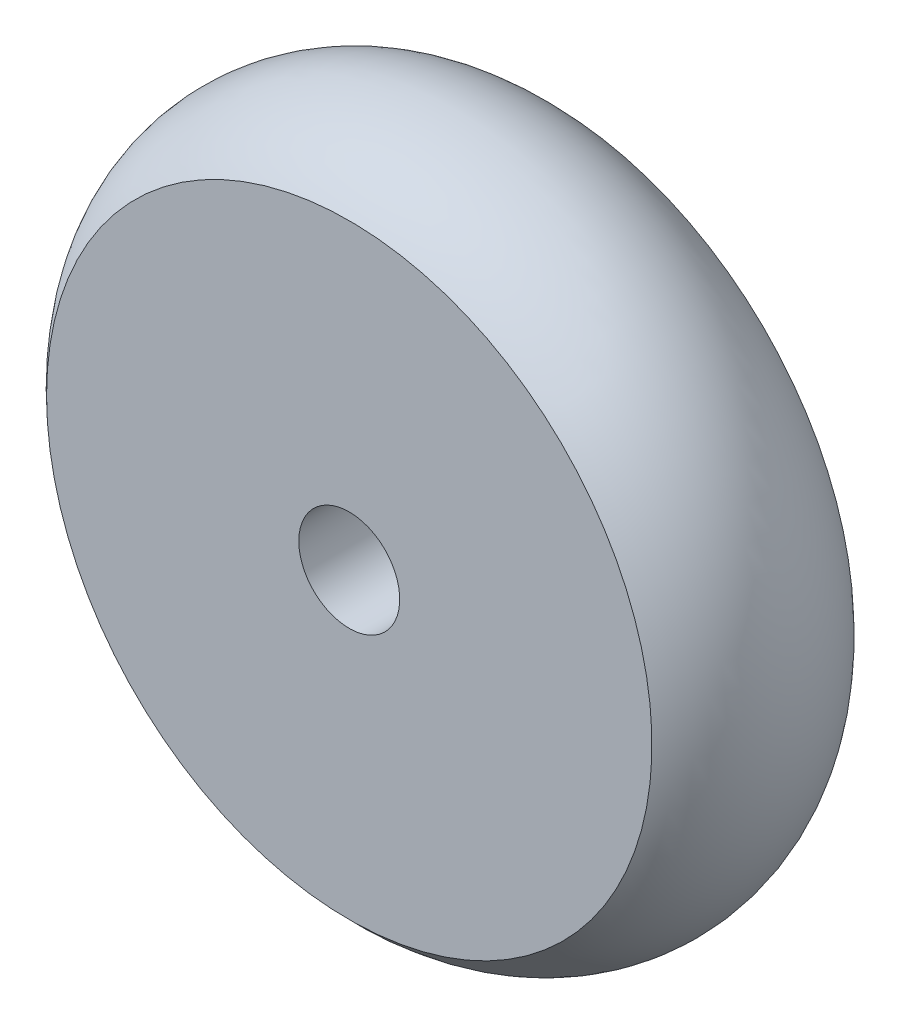
SolidWorks part; units mm, degrees
material "Латунь"
ref_plane "Front" through (0, 0, 0) normal (0, 0, 1) x (1, 0, 0)
ref_plane "Top" through (0, 0, 0) normal (0, 1, 0) x (1, 0, 0)
ref_plane "Right" through (0, 0, 0) normal (1, 0, 0) x (0, 0, -1)
ref_axis "Ось1" through (0, 0, 50) along (0, 0, -1)
sketch "Эскиз1" plane through (0, 0, 0) normal (0, 1, 0) x (1, 0, 0)
  line L14 (0, 0) -> (0, -8.0264) construction
  line L21 (-4.5, -3) -> (-0.75, -3)
  line L23 (-0.75, -3) -> (-0.75, -1)
  line L24 (-0.75, -1) -> (0, -1)
  line L25 (0, -1) -> (0, 0)
  line L26 (0, 0) -> (-4.5, 0)
  arc A1 (-4.5, 0) -> (-4.5, -3) centre (-3.1771, -1.5) ccw
  point P2 (-5.1771, -1.5)
  dimension "D1" = 3
  dimension "D2" = 2
  dimension "D3" = 9
  dimension "D4" = 1.5
  dimension "D5" = 1
revolve "Повернуть2" add sketch "Эскиз1" angle 360 about L14
chamfer "Фаска1" [suppressed] distance 0.3 angle 20
